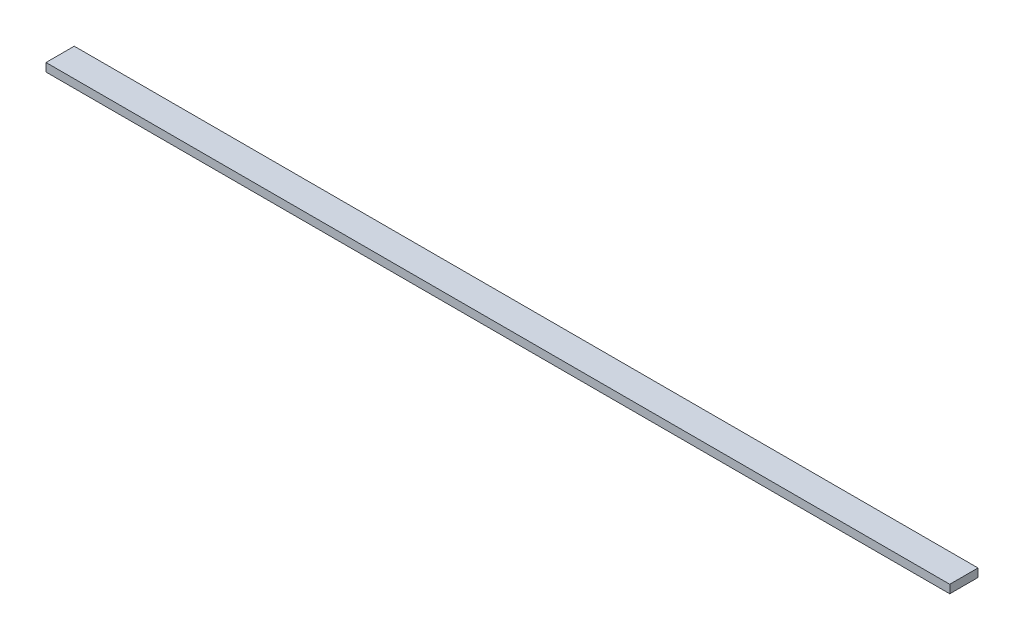
SolidWorks part; units mm, degrees
material "Rubber"
ref_plane "Front" through (0, 0, 0) normal (0, 0, 1) x (1, 0, 0)
ref_plane "Top" through (0, 0, 0) normal (0, 1, 0) x (1, 0, 0)
ref_plane "Right" through (0, 0, 0) normal (1, 0, 0) x (0, 0, -1)
sketch "Sketch1" plane through (0, 0, 0) normal (0, 1, 0) x (1, 0, 0)
  line L1 (-304.8, 9.525) -> (304.8, 9.525)
  line L2 (-304.8, 9.525) -> (-304.8, -9.525)
  line L3 (-304.8, -9.525) -> (304.8, -9.525)
  line L4 (304.8, 9.525) -> (304.8, -9.525)
  line L5 (-304.8, 9.525) -> (304.8, -9.525) construction
  line L6 (-304.8, -9.525) -> (304.8, 9.525) construction
  point P0 (0, 0)
  dimension "D1" = 19.05
  dimension "D2" = 609.6
extrude "Boss-Extrude1" add sketch "Sketch1" along normal blind 5.588
